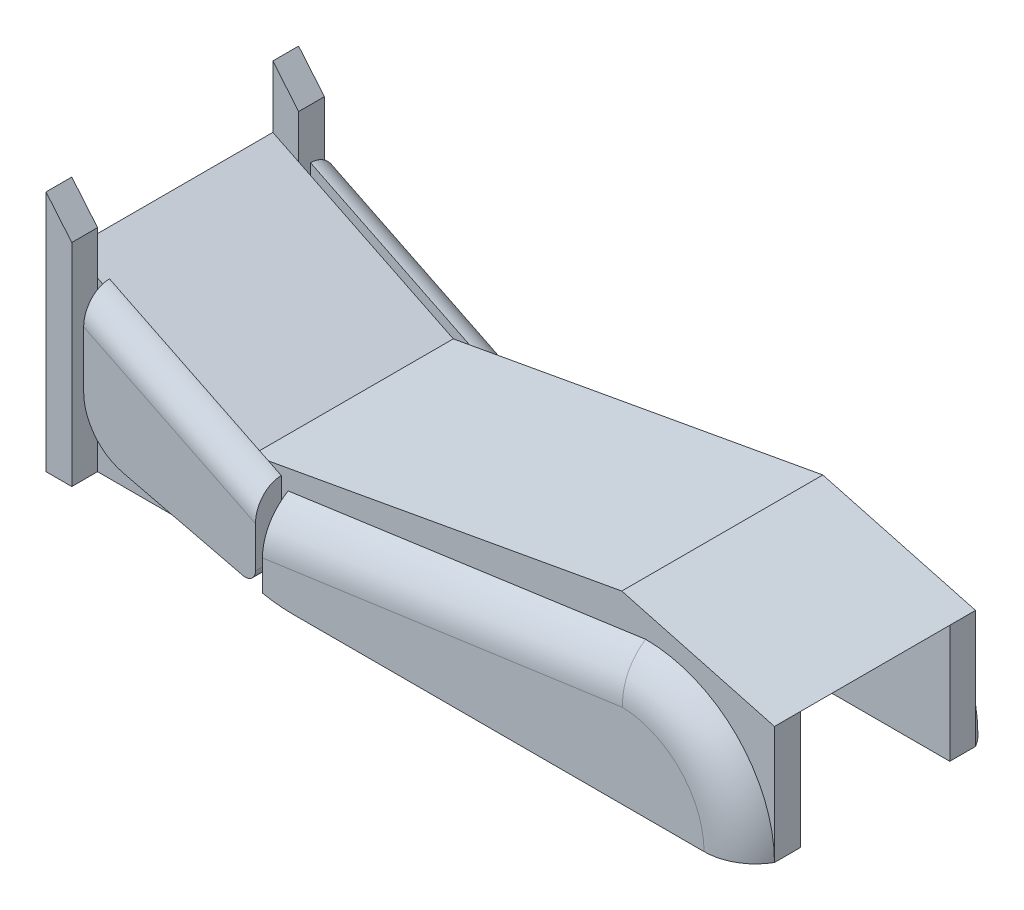
SolidWorks part; units mm, degrees
ref_plane "Front Plane" through (0, 0, 0) normal (0, 0, 1) x (1, 0, 0)
ref_plane "Top Plane" through (0, 0, 0) normal (0, 1, 0) x (1, 0, 0)
ref_plane "Right Plane" through (0, 0, 0) normal (1, 0, 0) x (0, 0, -1)
sketch "Sketch1" plane through (0, 0, 0) normal (0, 0, 1) x (1, 0, 0)
  line L0 (0, 0) -> (-90, 0) construction
  line L1 (0, 0) -> (-101.3014, 27.1436)
  line L2 (-101.3014, 27.1436) -> (-101.3014, -22.8564)
  line L3 (-101.3014, -22.8564) -> (0, -22.8564)
  line L4 (0, -2.2) -> (0, -44.3) construction
  line L5 (0, -22.8564) -> (0, 0)
  dimension "D1" = 90
  dimension "D2" = 15
  dimension "D3" = 50
extrude "Boss-Extrude1" add sketch "Sketch1" along normal blind 5
sketch "Sketch3" plane through (0, 0, 0) normal (0, 0, -1) x (-1, 0, 0)
  line L0 (101.3014, 27.1436) -> (101.3014, -22.8564)
  line L1 (101.3014, -22.8564) -> (28.3, -22.8564)
  line L2 (101.3014, -22.8564) -> (0, -22.8564) construction
  line L3 (28.3, -20.8) -> (28.3, -30.2) construction
  line L4 (28.3, -22.8564) -> (28.3, 0)
  line L5 (28.3, 0) -> (0, 0)
  line L6 (0, 0) -> (101.3014, 27.1436)
extrude "Boss-Extrude3" add sketch "Sketch3" along normal up to surface (29 mm away)
sketch "Sketch7" plane through (0, -22.8564, 0) normal (0, -1, 0) x (1, 0, 0)
  line L0 (-28.3, -14.5) -> (-38.3, -14.5) construction
  line L1 (-28.3, -29) -> (-28.3, 0) construction
  line L2 (-38.3, -14.5) -> (-38.3, -6.5) construction
  line L3 (-94.3028, -14.5) -> (-38.3, -14.5) construction
  line L7 (-66.3014, -14.5) -> (-66.3014, -29) construction
  line L8 (-28.3, -29) -> (-101.3014, -29) construction
  circle A0 centre (-38.3, -6.5) radius 2.55
  circle A1 centre (-38.3, -22.5) radius 2.55
  circle A2 centre (-94.3028, -22.5) radius 2.55
  circle A3 centre (-94.3028, -6.5) radius 2.55
  dimension "D3" = 5.1
  dimension "D1" = 10
  dimension "D2" = 8
extrude "Cut-Extrude1" cut sketch "Sketch7" against normal blind 4
sketch "Sketch8" plane through (0, 0, -29) normal (0, 0, -1) x (-1, 0, 0)
  line L0 (0, 0) -> (0, -22.8564)
  line L1 (0, -22.8564) -> (28.3, -22.8564)
  line L5 (101.3014, -22.8564) -> (101.3014, 27.1436)
  line L6 (101.3014, 27.1436) -> (0, 0)
  line L7 (0, 0) -> (28.3, 0)
  line L8 (28.3, 0) -> (28.3, -22.8564)
  line L9 (28.3, -22.8564) -> (101.3014, -22.8564)
  line L10 (101.3014, -22.8564) -> (101.3014, 27.1436)
  line L11 (101.3014, 27.1436) -> (0, 0)
  line L14 (28.3, -22.8564) -> (101.3014, -22.8564)
  dimension "D1" = 0
extrude "Boss-Extrude4" add sketch "Sketch8" along normal blind 5
sketch "Sketch9" plane through (0, 0, -34) normal (0, 0, -1) x (-1, 0, 0)
  line L0 (101.3014, 27.1436) -> (29.6215, 7.9371)
  line L1 (101.3014, 27.1436) -> (0, 0) construction
  line L2 (29.6215, 7.9371) -> (101.3014, -5.0413)
  line L3 (101.3014, -22.8564) -> (101.3014, 27.1436) construction
  line L4 (101.3014, -5.0413) -> (101.3014, 27.1436)
extrude "Cut-Extrude2" cut sketch "Sketch9" against normal blind 50
sketch "Sketch10" plane through (0, 0, 5) normal (0, 0, 1) x (1, 0, 0)
  line L0 (-101.3014, -22.8564) -> (-136.3014, -22.8564)
  line L1 (-136.3014, -22.8564) -> (-136.3014, 12.1436)
  line L2 (-136.3014, 12.1436) -> (-101.3014, -5.0413)
  line L3 (-101.3014, -5.0413) -> (-101.3014, -22.8564)
  dimension "D1" = 35
  dimension "D2" = 35
extrude "Boss-Extrude5" add sketch "Sketch10" against normal up to surface (39 mm away) up to face at (-46.4449, -8.5634, -34)
sketch "Sketch11" plane through (0, 0, 5) normal (0, 0, 1) x (1, 0, 0)
  line L0 (-136.3014, -22.8564) -> (-131.3014, -22.8564)
  line L1 (-136.3014, -22.8564) -> (0, -22.8564) construction
  line L2 (-136.3014, -22.8564) -> (-136.3014, 24.1436)
  line L3 (-131.3014, -22.8564) -> (-131.3014, 18.1435)
  line L4 (-131.3014, 18.1435) -> (-136.3014, 24.1436)
  dimension "D1" = 5
  dimension "D2" = 47
extrude "Boss-Extrude6" add sketch "Sketch11" along normal blind 5
sketch "Sketch12" plane through (0, 0, -34) normal (0, 0, -1) x (-1, 0, 0)
  line L4 (136.3014, -22.8564) -> (136.3014, 24.1436)
  line L5 (131.3014, -22.8564) -> (136.3014, -22.8564)
  line L6 (131.3014, 18.1435) -> (131.3014, -22.8564)
  line L7 (136.3014, 24.1436) -> (131.3014, 18.1435)
  line L8 (136.3014, -22.8564) -> (136.3014, 24.1436)
  line L9 (131.3014, -22.8564) -> (136.3014, -22.8564)
  line L10 (131.3014, 18.1435) -> (131.3014, -22.8564)
  line L11 (136.3014, 24.1436) -> (131.3014, 18.1435)
  dimension "D1" = 0
extrude "Boss-Extrude7" add sketch "Sketch12" along normal blind 5
sketch "Sketch13" plane through (0, 0, 5) normal (0, 0, 1) x (1, 0, 0)
  line L0 (0, -22.8564) -> (-80, -22.8564)
  line L1 (-131.3014, -22.8564) -> (0, -22.8564) construction
  line L2 (-25, -22.8564) -> (-25, 2.1436) construction
  line L3 (0, -22.8564) -> (0, 0) construction
  line L4 (-25, 2.1436) -> (-94.3188, -7.5985)
  line L5 (-94.3188, -22.2613) -> (-94.3188, -22.8564)
  line L6 (-88.3733, -22.8564) -> (-80, -22.8564)
  line L11 (-94.3188, -22.2613) -> (-94.3188, -7.5985)
  arc A0 (0, -22.8564) -> (-25, 2.1436) centre (-25, -22.8564) ccw
  arc A1 (-88.3733, -22.8564) -> (-94.3188, -22.2613) centre (-88.3733, 7.1436) cw
  line M11 (-131.3014, 9.6886) -> (-131.3014, -22.8564)
  line M12 (-131.3014, -22.8564) -> (0, -22.8564)
  line M15 (-29.6215, 7.9371) -> (-101.3014, -5.0413)
  line M16 (-101.3014, -5.0413) -> (-131.3014, 9.6886)
  dimension "D7" = 30
  dimension "D1" = 80
  dimension "D2" = 25
  dimension "D3" = 82
  dimension "D4" = 70
extrude "Boss-Extrude8" add sketch "Sketch13" along normal blind 5 contours L2 L4 A1 M12 M15 M16 M11 | L2 L0 A0 region at (-14.3897, -12.246, 5) region at (-56.8333, -12.5869, 5)
fillet "Fillet1" radius 10 2 edges at (-59.6594, -2.7274, 10) (-7.3223, -5.1787, 10)
sketch "Sketch14" plane through (0, 0, 5) normal (0, 0, 1) x (1, 0, 0)
  line L2 (-128.9911, 10.6977) -> (-95.6694, -5.689)
  line L3 (-128.9911, -13.7249) -> (-95.6694, -21.7844)
  line L4 (-95.6694, -21.7844) -> (-95.6694, -5.689)
  line L5 (-128.9911, 10.6977) -> (-128.9911, -13.7249)
extrude "Boss-Extrude9" add sketch "Sketch14" along normal blind 5
fillet "Fillet2" radius 10 1 edges at (-128.9911, -13.7249, 7.5)
fillet "Fillet3" radius 5 1 edges at (-112.3302, 2.5043, 10)
fillet "Fillet4" radius 2 1 edges at (-95.6694, -21.7844, 7.5)
sketch "Sketch15" plane through (0, 0, -34) normal (0, 0, -1) x (-1, 0, 0)
  line L0 (88.3733, -22.8564) -> (80, -22.8564) construction
  line L1 (94.3188, -22.2613) -> (94.3188, -7.5985) construction
  line L2 (25, 2.1436) -> (94.3188, -7.5985) construction
  line L3 (0, -22.8564) -> (80, -22.8564) construction
  line L4 (88.3733, -22.8564) -> (80, -22.8564)
  line L5 (94.3188, -22.2613) -> (94.3188, -7.5985)
  line L18 (25, 2.1436) -> (94.3188, -7.5985)
  line L19 (0, -22.8564) -> (80, -22.8564)
  arc A1 (88.3733, -22.8564) -> (94.3188, -22.2613) centre (88.3733, 7.1436) ccw construction
  arc A2 (25, 2.1436) -> (0, -22.8564) centre (25, -22.8564) ccw construction
  arc A3 (88.3733, -22.8564) -> (94.3188, -22.2613) centre (88.3733, 7.1436) ccw
  arc A4 (25, 2.1436) -> (0, -22.8564) centre (25, -22.8564) ccw
extrude "Boss-Extrude10" add sketch "Sketch15" along normal blind 5
fillet "Fillet5" radius 10 2 edges at (-59.6594, -2.7274, -39) (-7.3223, -5.1787, -39)
sketch "Sketch16" plane through (0, 0, -34) normal (0, 0, -1) x (-1, 0, 0)
  line L0 (128.9911, 10.6977) -> (95.6694, -5.689) construction
  line L1 (128.9911, 10.6977) -> (95.6694, -5.689)
  line L2 (95.6694, -21.7844) -> (95.6694, -5.689) construction
  line L3 (95.6694, -21.7844) -> (95.6694, -5.689)
  line L4 (128.9911, -13.7249) -> (95.6694, -21.7844) construction
  line L5 (128.9911, 10.6977) -> (128.9911, -13.7249) construction
  line L6 (128.9911, -13.7249) -> (95.6694, -21.7844)
  line L7 (128.9911, 10.6977) -> (128.9911, -13.7249)
extrude "Boss-Extrude11" add sketch "Sketch16" along normal blind 5
fillet "Fillet6" radius 10 1 edges at (-128.9911, -13.7249, -36.5)
fillet "Fillet7" radius 5 1 edges at (-112.3302, 2.5043, -39)
fillet "Fillet8" radius 2 1 edges at (-95.6694, -21.7844, -36.5)
